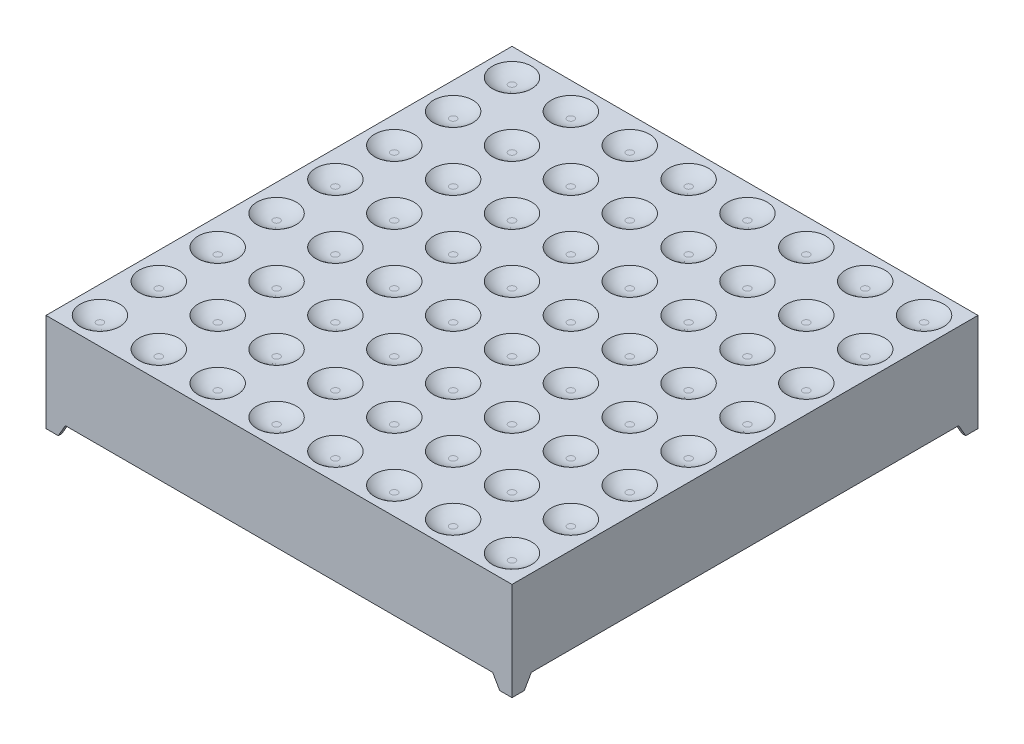
SolidWorks part; units mm, degrees
ref_plane "Front" through (0, 0, 0) normal (0, 0, 1) x (1, 0, 0)
ref_plane "Top" through (0, 0, 0) normal (0, 1, 0) x (1, 0, 0)
ref_plane "Right" through (0, 0, 0) normal (1, 0, 0) x (0, 0, -1)
sketch "Sketch1" plane through (0, 0, 0) normal (0, 1, 0) x (1, 0, 0)
  line L1 (-19, -19) -> (19, -19)
  line L2 (-19, -19) -> (-19, 19)
  line L3 (-19, 19) -> (19, 19)
  line L4 (19, -19) -> (19, 19)
  line L5 (-19, -19) -> (19, 19) construction
  line L6 (-19, 19) -> (19, -19) construction
  point P0 (0, 0)
  dimension "D1" = 38
extrude "Boss-Extrude1" add sketch "Sketch1" along normal mid plane 8
sketch "Sketch2" plane through (0, -4, 0) normal (0, -1, 0) x (1, 0, 0)
  line L0 (-19, -19) -> (-19, 19) construction
  line L1 (18.7, 18.7) -> (-18.7, 18.7)
  line L2 (18.7, 18.7) -> (18.7, -18.7)
  line L3 (18.7, -18.7) -> (-18.7, -18.7)
  line L4 (-18.7, 18.7) -> (-18.7, -18.7)
  line L5 (18.7, 18.7) -> (-18.7, -18.7) construction
  line L6 (18.7, -18.7) -> (-18.7, 18.7) construction
  line L7 (19, -19) -> (-19, -19) construction
  point P0 (0, 0)
  dimension "D1" = 0.3
  dimension "D2" = 0.3
extrude "Cut-Extrude1" cut sketch "Sketch2" against normal blind 1.5
sketch "Sketch3" plane through (0, 0, 19) normal (0, 0, 1) x (1, 0, 0)
  line L0 (-18, -4) -> (-17.4226, -3)
  line L1 (-19, -4) -> (19, -4) construction
  line L2 (-17.4226, -3) -> (17.4226, -3)
  line L3 (0, -3) -> (0, 0) construction
  line L4 (-19, 4) -> (-19, -4) construction
  line L5 (18, -4) -> (17.4226, -3)
  line L6 (-18, -4) -> (18, -4)
  dimension "D1" = 1
  dimension "D2" = 60
  dimension "D3" = 1
extrude "Cut-Extrude2" cut sketch "Sketch3" against normal through all
sketch "Sketch4" plane through (-19, 0, 0) normal (-1, 0, 0) x (0, 0, 1)
  line L0 (-18, -4) -> (-17.4226, -3)
  line L1 (-19, -4) -> (19, -4) construction
  line L2 (-17.4226, -3) -> (17.4226, -3)
  line L3 (0, -3) -> (0, 0) construction
  line L4 (-19, 4) -> (-19, -4) construction
  line L5 (18, -4) -> (17.4226, -3)
  line L6 (-18, -4) -> (18, -4)
  dimension "D1" = 60
  dimension "D2" = 1
  dimension "D3" = 1
extrude "Cut-Extrude3" cut sketch "Sketch4" against normal through all
sketch "Sketch5" plane through (0, 4, 0) normal (0, 1, 0) x (1, 0, 0)
  line L1 (16.8, 16.8) -> (16.8, 12) construction
  line L2 (16.8, 16.8) -> (12, 16.8) construction
  line L3 (-16.8, 16.8) -> (16.8, -16.8) construction
  line L7 (16.8, 16.8) -> (-16.8, -16.8) construction
  circle A0 centre (-16.8, 16.8) radius 1.6
  circle A1 centre (-12, 16.8) radius 1.6
  circle A2 centre (-7.2, 16.8) radius 1.6
  circle A3 centre (-2.4, 16.8) radius 1.6
  circle A4 centre (2.4, 16.8) radius 1.6
  circle A5 centre (7.2, 16.8) radius 1.6
  circle A6 centre (12, 16.8) radius 1.6
  circle A7 centre (16.8, 16.8) radius 1.6
  circle A8 centre (-16.8, 12) radius 1.6
  circle A9 centre (-12, 12) radius 1.6
  circle A10 centre (-7.2, 12) radius 1.6
  circle A11 centre (-2.4, 12) radius 1.6
  circle A12 centre (2.4, 12) radius 1.6
  circle A13 centre (7.2, 12) radius 1.6
  circle A14 centre (12, 12) radius 1.6
  circle A15 centre (16.8, 12) radius 1.6
  circle A16 centre (-16.8, 7.2) radius 1.6
  circle A17 centre (-12, 7.2) radius 1.6
  circle A18 centre (-7.2, 7.2) radius 1.6
  circle A19 centre (-2.4, 7.2) radius 1.6
  circle A20 centre (2.4, 7.2) radius 1.6
  circle A21 centre (7.2, 7.2) radius 1.6
  circle A22 centre (12, 7.2) radius 1.6
  circle A23 centre (16.8, 7.2) radius 1.6
  circle A24 centre (-16.8, 2.4) radius 1.6
  circle A25 centre (-12, 2.4) radius 1.6
  circle A26 centre (-7.2, 2.4) radius 1.6
  circle A27 centre (-2.4, 2.4) radius 1.6
  circle A28 centre (2.4, 2.4) radius 1.6
  circle A29 centre (7.2, 2.4) radius 1.6
  circle A30 centre (12, 2.4) radius 1.6
  circle A31 centre (16.8, 2.4) radius 1.6
  circle A32 centre (-16.8, -2.4) radius 1.6
  circle A33 centre (-12, -2.4) radius 1.6
  circle A34 centre (-7.2, -2.4) radius 1.6
  circle A35 centre (-2.4, -2.4) radius 1.6
  circle A36 centre (2.4, -2.4) radius 1.6
  circle A37 centre (7.2, -2.4) radius 1.6
  circle A38 centre (12, -2.4) radius 1.6
  circle A39 centre (16.8, -2.4) radius 1.6
  circle A40 centre (-16.8, -7.2) radius 1.6
  circle A41 centre (-12, -7.2) radius 1.6
  circle A42 centre (-7.2, -7.2) radius 1.6
  circle A43 centre (-2.4, -7.2) radius 1.6
  circle A44 centre (2.4, -7.2) radius 1.6
  circle A45 centre (7.2, -7.2) radius 1.6
  circle A46 centre (12, -7.2) radius 1.6
  circle A47 centre (16.8, -7.2) radius 1.6
  circle A48 centre (-16.8, -12) radius 1.6
  circle A49 centre (-12, -12) radius 1.6
  circle A50 centre (-7.2, -12) radius 1.6
  circle A51 centre (-2.4, -12) radius 1.6
  circle A52 centre (2.4, -12) radius 1.6
  circle A53 centre (7.2, -12) radius 1.6
  circle A54 centre (12, -12) radius 1.6
  circle A55 centre (16.8, -12) radius 1.6
  circle A56 centre (-16.8, -16.8) radius 1.6
  circle A57 centre (-12, -16.8) radius 1.6
  circle A58 centre (-7.2, -16.8) radius 1.6
  circle A59 centre (-2.4, -16.8) radius 1.6
  circle A60 centre (2.4, -16.8) radius 1.6
  circle A61 centre (7.2, -16.8) radius 1.6
  circle A62 centre (12, -16.8) radius 1.6
  circle A63 centre (16.8, -16.8) radius 1.6
  point P2 (0, 0)
  dimension "D1" = 3.2
  dimension "D7" = 4.8
  dimension "D4" = 8
  dimension "D5" = 8
extrude "Cut-Extrude4" cut sketch "Sketch5" against normal blind 0.5
fillet "Fillet1" radius 2 64 edges at (-12, 3.5, 18.4) (-16.8, 3.5, 18.4) (-7.2, 3.5, 18.4) (-2.4, 3.5, 18.4) (2.4, 3.5, 18.4) (7.2, 3.5, 18.4) (12, 3.5, 18.4) (16.8, 3.5, 18.4) (-16.8, 3.5, 13.6) (-12, 3.5, 13.6) (-7.2, 3.5, 13.6) (-2.4, 3.5, 13.6) (12, 3.5, 13.6) (7.2, 3.5, 13.6) (2.4, 3.5, 13.6) (2.4, 3.5, 8.8) (-2.4, 3.5, 8.8) (-7.2, 3.5, 8.8) (-12, 3.5, 8.8) (-16.8, 3.5, 8.8) (-7.2, 3.5, 4) (-12, 3.5, 4) (-16.8, 3.5, 4) (-16.8, 3.5, -0.8) (16.8, 3.5, 13.6) (7.2, 3.5, 8.8) (12, 3.5, 8.8) (16.8, 3.5, 8.8) (-2.4, 3.5, 4) (2.4, 3.5, 4) (7.2, 3.5, 4) (12, 3.5, 4) (16.8, 3.5, 4) (-12, 3.5, -0.8) (-7.2, 3.5, -0.8) (-2.4, 3.5, -0.8) (2.4, 3.5, -0.8) (7.2, 3.5, -0.8) (12, 3.5, -0.8) (16.8, 3.5, -0.8) (2.4, 3.5, -5.6) (-2.4, 3.5, -5.6) (-7.2, 3.5, -5.6) (-12, 3.5, -5.6) (-16.8, 3.5, -5.6) (-7.2, 3.5, -10.4) (-12, 3.5, -10.4) (-16.8, 3.5, -10.4) (-16.8, 3.5, -15.2) (-12, 3.5, -15.2) (-7.2, 3.5, -15.2) (-2.4, 3.5, -15.2) (-2.4, 3.5, -10.4) (7.2, 3.5, -5.6) (16.8, 3.5, -5.6) (12, 3.5, -5.6) (2.4, 3.5, -15.2) (2.4, 3.5, -10.4) (7.2, 3.5, -10.4) (16.8, 3.5, -10.4) (12, 3.5, -10.4) (7.2, 3.5, -15.2) (16.8, 3.5, -15.2) (12, 3.5, -15.2)
sketch "Sketch6" plane through (0, -2.5, 0) normal (0, -1, 0) x (1, 0, 0)
  circle A0 centre (-9, 12) radius 0.255
  circle A1 centre (-6.4286, 12) radius 0.255
  circle A2 centre (-3.8571, 12) radius 0.255
  circle A3 centre (-1.2857, 12) radius 0.255
  circle A4 centre (1.2857, 12) radius 0.255
  circle A5 centre (3.8571, 12) radius 0.255
  circle A6 centre (6.4286, 12) radius 0.255
  circle A7 centre (9, 12) radius 0.255
  circle A8 centre (-9, -12) radius 0.255
  circle A9 centre (-6.4286, -12) radius 0.255
  circle A10 centre (-3.8571, -12) radius 0.255
  circle A11 centre (-1.2857, -12) radius 0.255
  circle A12 centre (1.2857, -12) radius 0.255
  circle A13 centre (3.8571, -12) radius 0.255
  circle A14 centre (6.4286, -12) radius 0.255
  circle A15 centre (9, -12) radius 0.255
  dimension "D1" = 0.51
  dimension "D2" = 9
  dimension "D3" = 12
  dimension "D7" = 9
  dimension "D8" = 2.5714
  dimension "D6" = 9
  dimension "D9" = 12
  dimension "D4" = 8
  dimension "D5" = 2
extrude "Boss-Extrude2" add sketch "Sketch6" along normal blind 6
